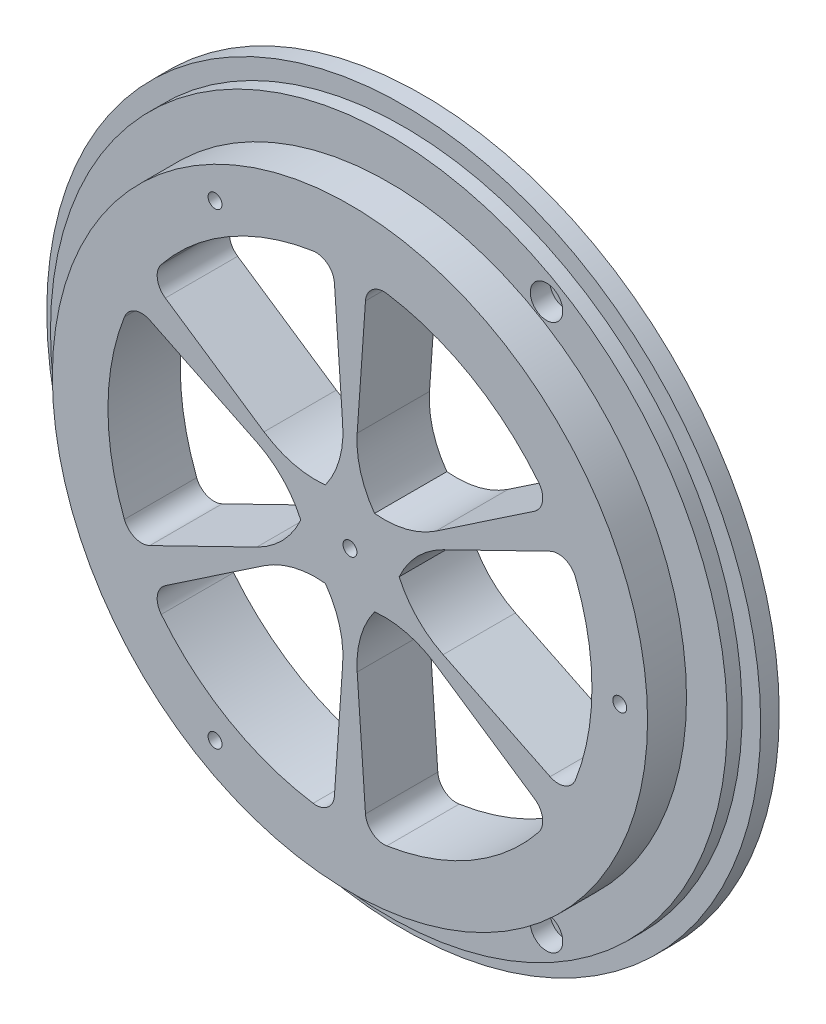
SolidWorks part; units mm, degrees
ref_plane "前视基准面" through (0, 0, 0) normal (0, 0, 1) x (1, 0, 0)
ref_plane "上视基准面" through (0, 0, 0) normal (0, 1, 0) x (1, 0, 0)
ref_plane "右视基准面" through (0, 0, 0) normal (1, 0, 0) x (0, 0, -1)
other "Configuration Table"
sketch "草图1" plane through (0, 0, 0) normal (0, 0, 1) x (1, 0, 0)
  circle A0 centre (0, 0) radius 32.1
  dimension "D1" = 64.2
extrude "凸台-拉伸1" add sketch "草图1" along normal blind 5 contours A0
sketch "草图2" plane through (0, 0, 0) normal (0, 0, -1) x (-1, 0, 0)
  circle A0 centre (0, 0) radius 36.5
  dimension "D1" = 73
extrude "凸台-拉伸2" add sketch "草图2" along normal blind 1.6 from offset 0.8 offset against normal yes
sketch "草图3" plane through (0, 0, -0.8) normal (0, 0, -1) x (-1, 0, 0)
  circle A0 centre (0, 0) radius 38.5
  circle A1 centre (0, 0) radius 36.5 construction
  dimension "D1" = 2
extrude "凸台-拉伸3" add sketch "草图3" along normal blind 2
sketch "草图4" plane through (0, 0, 5) normal (0, 0, 1) x (1, 0, 0)
  line L0 (0, 0) -> (-1.8206, 26.0364)
  line L1 (0, 0) -> (1.8206, 26.0364)
  line L2 (0, 0) -> (0, 26.1) construction
  line L3 (-1.8206, 26.0364) -> (1.8206, 26.0364) construction
  circle A0 centre (0, 0) radius 5
  circle A1 centre (0, 0) radius 26.1
  circle A2 centre (0, 0) radius 32.1 construction
  point P7 (0, 26.0364)
  dimension "D1" = 10
  dimension "D2" = 6
  dimension "D3" = 8
extrude "切除-拉伸1" cut sketch "草图4" against normal through all contours A1
extrude "凸台-拉伸4" add sketch "草图4<3>" against normal through all separate body contours A0
sketch "草图4<3>" plane through (0, 0, 5) normal (0, 0, 1) x (1, 0, 0) same geometry as "草图4"
extrude "凸台-拉伸5" add sketch "草图4<4>" against normal through all contours L1 A1 L0 A0 region at (0, 17.9213, 5)
sketch "草图4<4>" plane through (0, 0, 5) normal (0, 0, 1) x (1, 0, 0) same geometry as "草图4"
fillet "圆角6" radius 2 2 edges at (1.8206, 26.0364, 1.1) (-1.8206, 26.0364, 1.1)
pattern_circular "阵列(圆周)2" count 6 over 360 about axis through (0, 0, 5) along (0, 0, -1) of "圆角6", "凸台-拉伸5"
fillet "圆角7" radius 10 12 edges at (-4.494, -2.1919, 1.1) (-4.1452, -2.796, 1.1) (-0.3488, -4.9878, 1.1) (4.1452, -2.796, 1.1) (0.3488, -4.9878, 1.1) (4.494, -2.1919, 1.1) (4.494, 2.1919, 1.1) (4.1452, 2.796, 1.1) (0.3488, 4.9878, 1.1) (-0.3488, 4.9878, 1.1) (-4.1452, 2.796, 1.1) (-4.494, 2.1919, 1.1)
sketch "草图6" plane through (0, 0, 5) normal (0, 0, 1) x (1, 0, 0)
  line L0 (0, 0) -> (-14.55, 25.2013) construction
  line L1 (0, 0) -> (29.1, 0) construction
  line L2 (-14.55, -25.2013) -> (0, 0) construction
  line L3 (0, 0) -> (0, 29.1) construction
  circle A0 centre (0, 0) radius 0.75
  circle A1 centre (-14.55, 25.2013) radius 0.75
  circle A2 centre (29.1, 0) radius 0.75
  circle A3 centre (-14.55, -25.2013) radius 0.75
  circle A4 centre (0, 0) radius 29.1 construction
  circle A5 centre (0, 29.1) radius 3 construction
  arc A6 (-3.9751, 25.7955) -> (-20.352, 16.3403) centre (0, 0) ccw construction
  circle A8 centre (0, 0) radius 32.1 construction
  dimension "D4" = 1.5
  dimension "D1" = 30
  dimension "D2" = 120
  dimension "D3" = 120
extrude "切除-拉伸2" cut sketch "草图6" against normal blind 3 contours A3 | A2 | A1 | A0
sketch "草图8" plane through (0, 0, 0.8) normal (0, 0, 1) x (1, 0, 0)
  line L0 (0, -0.7766) -> (0, 33.2168) construction
  line L1 (-34, 0) -> (0, 0) construction
  line L2 (0, 0) -> (17, 29.4449) construction
  line L3 (0, 0) -> (17, -29.4449) construction
  circle A0 centre (0, 0) radius 34 construction
  circle A3 centre (17, 29.4449) radius 1
  circle A4 centre (-34, 0) radius 1
  circle A5 centre (17, -29.4449) radius 1
  circle A6 centre (-34, 0) radius 1.75
  circle A7 centre (17, 29.4449) radius 1.75
  circle A8 centre (17, -29.4449) radius 1.75
  dimension "D1" = 68
  dimension "D2" = 2
  dimension "D3" = 3.5
  dimension "D4" = 90
  dimension "D5" = 120
  dimension "D6" = 120
extrude "切除-拉伸4" cut sketch "草图8" against normal through all contours A4 | A5 | A3
extrude "切除-拉伸5" cut sketch "草图8<3>" against normal offset from surface (2.1 mm away) 1.5 contours A6 | A7 | A8 up to face at (-33, 0, -2.8)
sketch "草图8<3>" plane through (0, 0, 0.8) normal (0, 0, 1) x (1, 0, 0) same geometry as "草图8"
